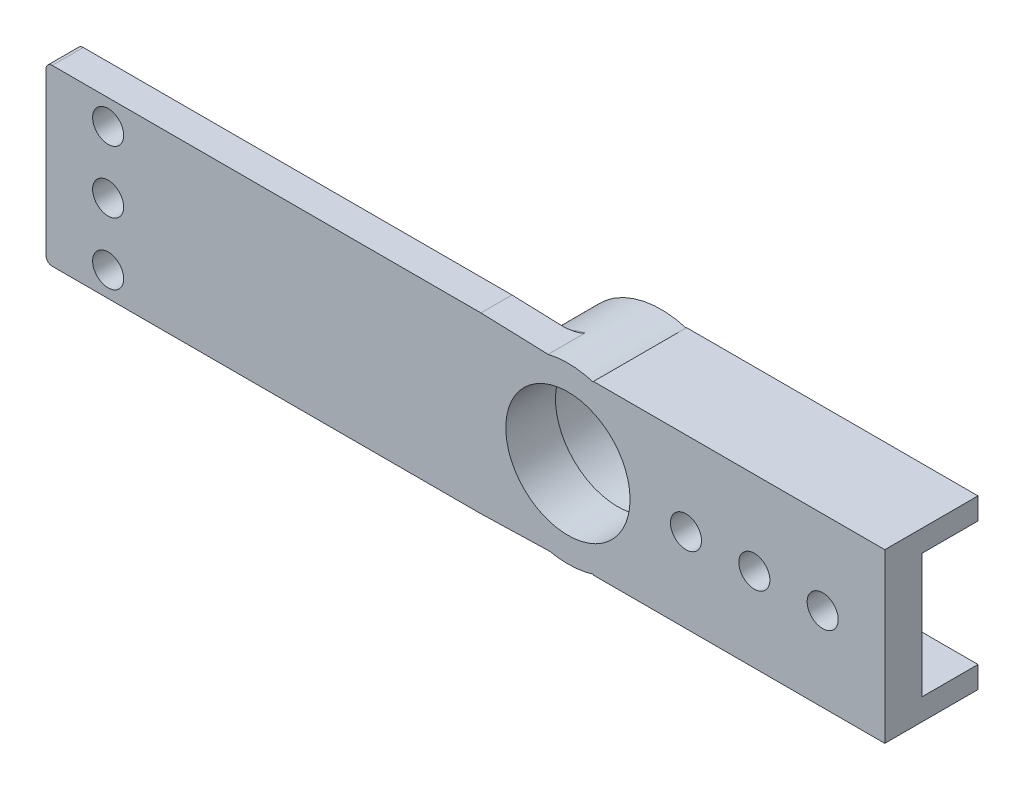
SolidWorks part; units mm, degrees
ref_plane "前视基准面" through (0, 0, 0) normal (0, 0, 1) x (1, 0, 0)
ref_plane "上视基准面" through (0, 0, 0) normal (0, 1, 0) x (1, 0, 0)
ref_plane "右视基准面" through (0, 0, 0) normal (1, 0, 0) x (0, 0, -1)
sketch "草图1" plane through (0, 0, 0) normal (0, 0, 1) x (1, 0, 0)
  line L1 (20, -10) -> (-20, -10)
  line L2 (20, -10) -> (20, 10)
  line L3 (20, 10) -> (-20, 10)
  line L4 (-20, -10) -> (-20, 10)
  line L5 (20, -10) -> (-20, 10) construction
  line L6 (20, 10) -> (-20, -10) construction
  point P0 (0, 0)
  dimension "D1" = 40
  dimension "D2" = 20
extrude "凸台-拉伸1" add sketch "草图1" along normal blind 6
sketch "草图2" plane through (0, 0, 6) normal (0, 0, 1) x (1, 0, 0)
  line L0 (20, -10) -> (20, 10) construction
  circle A0 centre (10, 0) radius 2.5
  circle A1 centre (-1, 0) radius 2.5
  circle A2 centre (-12, 0) radius 2.5
  dimension "D1" = 10
  dimension "D2" = 5
  dimension "D3" = 3
extrude "切除-拉伸1" cut sketch "草图2" against normal through all
sketch "草图3" plane through (0, 0, 6) normal (0, 0, 1) x (1, 0, 0)
  line L0 (20, 13.5) -> (20, 10)
  line L1 (20, -13.5) -> (-26.894, -13.5)
  line L3 (20, 13.5) -> (-26.894, 13.5)
  line L4 (-20, 10) -> (-20, -10)
  line L5 (-20, -10) -> (20, -10)
  line L6 (20, -10) -> (20, 10)
  line L7 (20, 10) -> (-20, 10)
  line L8 (-20, 10) -> (-20, -10)
  line L9 (-20, -10) -> (20, -10)
  line L10 (20, -10) -> (20, 10)
  line L11 (20, 10) -> (-20, 10)
  line L12 (-26.894, -13.5) -> (-26.894, 13.5)
  line L13 (20, -10.0394) -> (-26.894, 13.5) construction
  line L14 (20, 10.0394) -> (-26.894, -13.5) construction
  line L15 (20, -10) -> (20, -13.5)
  circle A0 centre (-31, 0) radius 11
  circle A1 centre (-31, 0) radius 14
  point P2 (0, 0)
  line M10 (-20, 10) -> (-20, -10)
  line M11 (-20, -10) -> (20, -10)
  line M13 (20, 10) -> (-20, 10)
  dimension "D3" = 22
  dimension "D4" = 28
  dimension "D2" = 3.5
  dimension "D1" = 0
extrude "凸台-拉伸2" add sketch "草图3" against normal blind 15 contours L3 A1 L1 L12 A0 | A1 L1 L15 M11 M10 | L1 A1 L8 A0 L12 | L8 A1 L3 L12 A0 | L8 A1 | A1 L0 L3 M10 M13 region at (-1.9449, 11.7771, 6) region at (-1.9449, -11.7771, 6) region at (-23.0173, 9.0328, 6) region at (-27.2274, 11.7946, 6) region at (-18.7882, 0, 6) region at (-23.0173, -9.0328, 6)
sketch "草图5" plane through (0, 0, 6) normal (0, 0, 1) x (1, 0, 0)
  circle A0 centre (-31, 0) radius 10
  circle A1 centre (-31, 0) radius 11 construction
  circle A2 centre (-31, 0) radius 11
  dimension "D1" = 20
extrude "凸台-拉伸3" add sketch "草图5" against normal blind 8
sketch "草图6" plane through (0, 0, 6) normal (0, 0, 1) x (1, 0, 0)
  circle A0 centre (-31, 0) radius 8.5
  circle A1 centre (-31, 0) radius 10 construction
  circle A2 centre (-31, 0) radius 10
  dimension "D1" = 17
sketch "草图8" plane through (0, 0, 6) normal (0, 0, 1) x (1, 0, 0)
  line L0 (20, -13.5) -> (20, 13.5) construction
  line L1 (20, -13.5) -> (-26.894, -13.5) construction
  line L2 (20, 13.5) -> (-26.894, 13.5) construction
  line L3 (20, -13.5) -> (20, 13.5)
  line L4 (20, -13.5) -> (-26.894, -13.5)
  line L5 (20, 13.5) -> (-26.894, 13.5)
  line L6 (-45, -14) -> (-26.894, -13.5)
  line L7 (-45, -14) -> (-115, -14)
  line L8 (-45, -14) -> (-45, 14)
  line L9 (-45, 14) -> (-115, 14)
  line L10 (-115, -14) -> (-115, 14)
  line L11 (-45, -14) -> (-115, 14) construction
  line L12 (-45, 14) -> (-115, -14) construction
  line L13 (-45, 14) -> (-26.894, 13.3843)
  line L14 (-12, 0) -> (-31, 0)
  arc A0 (-26.894, 13.3843) -> (-26.894, -13.3843) centre (-31, 0) ccw construction
  arc A1 (-26.894, 13.3843) -> (-26.894, -13.3843) centre (-31, 0) ccw
  point P6 (-80, 0)
  arc M11 (-26.894, 13.3843) -> (-26.894, -13.3843) centre (-31, 0) ccw
  dimension "D1" = 28
  dimension "D2" = 70
  dimension "D3" = 14
extrude "凸台-拉伸4" add sketch "草图8" against normal blind 5 contours L10 L7 L8 L9 | L8 L6 M11 | L13 L8 M11 region at (-42.1177, -10.7223, 6) region at (-80, 0, 6) region at (-42.1603, 10.6928, 6)
fillet "圆角1" radius 1 1 edges at (-44.9993, -0.1411, 1)
fillet "圆角2" radius 1 2 edges at (-115, 14, 3.5) (-115, -14, 3.5)
sketch "草图9" plane through (0, 0, 6) normal (0, 0, 1) x (1, 0, 0)
  line L0 (-115, 0) -> (-105, 0) construction
  line L1 (-115, -13) -> (-115, 13) construction
  circle A0 centre (-105, 0) radius 2.5
  circle A1 centre (-105, 10) radius 2.5
  circle A2 centre (-105, -10) radius 2.5
  dimension "D2" = 2
  dimension "5" = 5
  dimension "D1" = 10
  dimension "D3" = 2
extrude "切除-拉伸2" cut sketch "草图9" against normal blind 5
